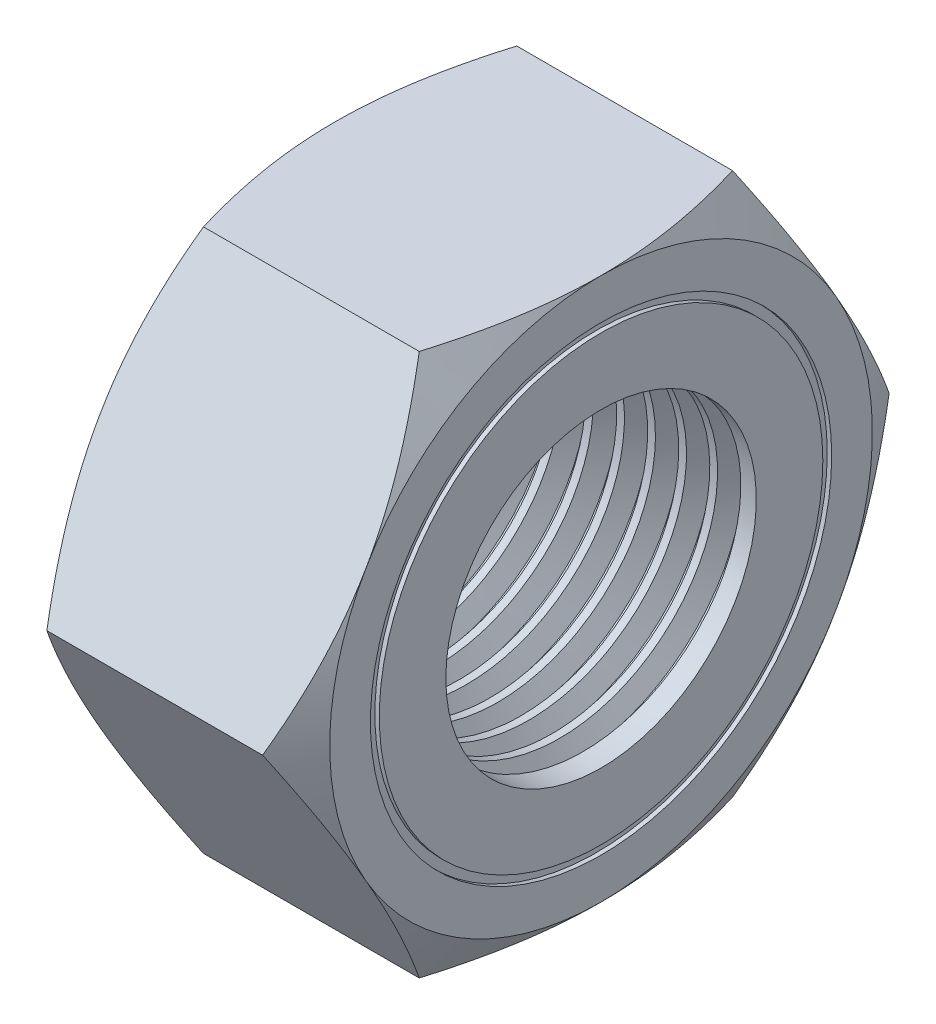
SolidWorks part; units mm, degrees
material "Cast Alloy Steel"
ref_plane "Front Plane" through (0, 0, 0) normal (0, 0, 1) x (1, 0, 0)
ref_plane "Top Plane" through (0, 0, 0) normal (0, 1, 0) x (1, 0, 0)
ref_plane "Right Plane" through (0, 0, 0) normal (1, 0, 0) x (0, 0, -1)
sketch "Sketch1" plane through (0, 0, 0) normal (1, 0, 0) x (0, 0, -1)
  line L1 (7.0633, 0) -> (3.5317, 6.117)
  line L2 (3.5317, 6.117) -> (-3.5317, 6.117)
  line L3 (-3.5317, 6.117) -> (-7.0633, 0)
  line L4 (-7.0633, 0) -> (-3.5317, -6.117)
  line L5 (-3.5317, -6.117) -> (3.5317, -6.117)
  line L6 (3.5317, -6.117) -> (7.0633, 0)
  circle A0 centre (0, 0) radius 6.117 construction
  circle A1 centre (0, 0) radius 3.5
  dimension "D1" = 7
extrude "Boss-Extrude1" add sketch "Sketch1" along normal blind 6
sketch "Sketch2" plane through (0, 0, 0) normal (0, 0, 1) x (1, 0, 0)
  line L0 (6, 6.117) -> (6, 8.117)
  line L1 (6, 8.117) -> (4.8, 8.117)
  line L2 (4.8, 8.117) -> (6, 6.117)
  line L3 (0, 0) -> (-3.4081, 0) construction
  line L5 (1.2, 8.117) -> (0, 6.117)
  line L6 (0, 8.117) -> (1.2, 8.117)
  line L7 (0, 6.117) -> (0, 8.117)
  dimension "D1" = 1.2
  dimension "D2" = 2
revolve "Cut-Revolve1" cut sketch "Sketch2" angle 360 about L3
sketch "Sketch3" plane through (6, 0, 0) normal (1, 0, 0) x (0, 0, -1)
  circle A0 centre (0, 0) radius 5
  circle A1 centre (0, 0) radius 5.2
  dimension "D1" = 10
  dimension "D2" = 0.2
extrude "Cut-Extrude1" cut sketch "Sketch3" against normal blind 0.1
thread "Thread1" pitch 0.7 method cut profile "Thread Profile1" start angle 0, offset 0, length 7, pitch 0.7, diameter 7
ref_plane "Plane1" through (6, 0, 3.5) normal (0, -1, 0) x (0, 0, 1)
sketch "Thread Profile1" plane through (6, 0, 3.5) normal (0, -1, 0) x (0, 0, 1)
  line L0 (0, 0) -> (0, 0.7) construction
  line L1 (0, 0) -> (0.3789, 0.2187)
  line L2 (0.3789, 0.2187) -> (0.3789, 0.3062)
  line L3 (0.3789, 0.3062) -> (0, 0.525)
  line L4 (0.3789, 0.2625) -> (0, 0.2625) construction
  line L11 (0, 0) -> (0, 0.525)
  point P2 (0, 0)
  dimension "Pitch" = 0.7
  dimension "Profile_Angle" = 60
  dimension "Profile_Land" = 0.0875
  dimension "Profile_Height" = 0.3789
